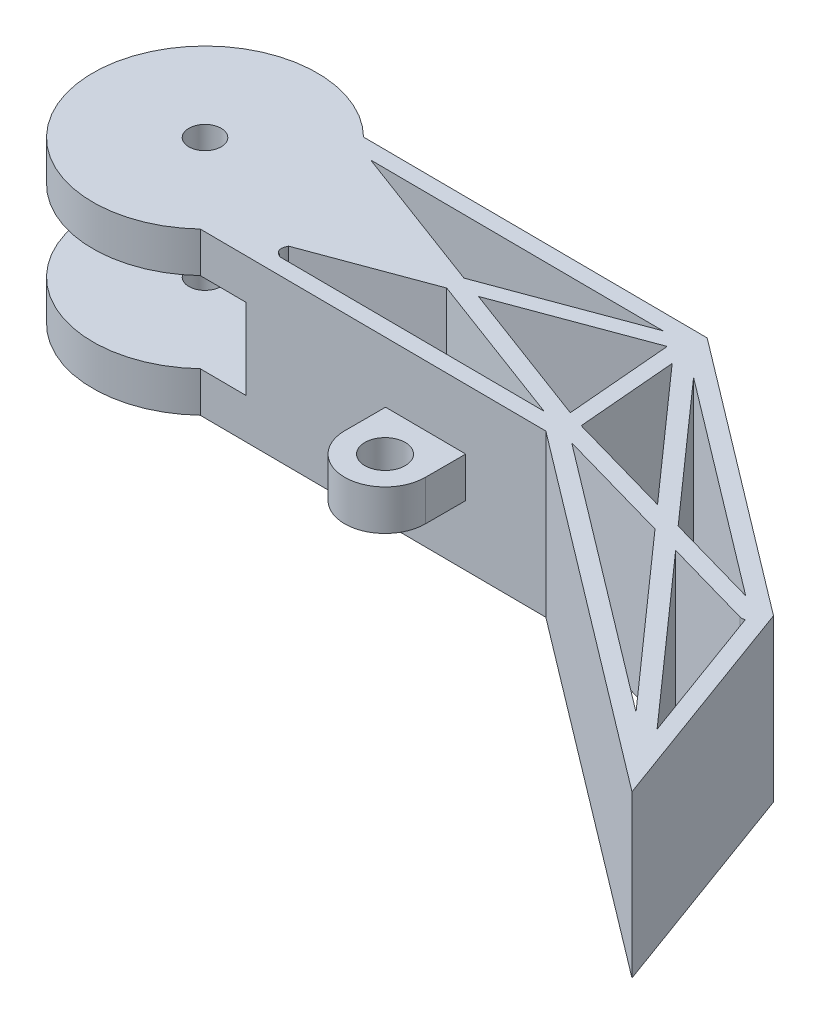
SolidWorks part; units mm, degrees
ref_plane "Front Plane" through (0, 0, 0) normal (0, 0, 1) x (1, 0, 0)
ref_plane "Top Plane" through (0, 0, 0) normal (0, 1, 0) x (1, 0, 0)
ref_plane "Right Plane" through (0, 0, 0) normal (1, 0, 0) x (0, 0, -1)
sketch "Sketch2" plane through (0, 0, 0) normal (0, 1, 0) x (1, 0, 0)
  line L0 (-86.903, -5.6011) -> (-1.9458, -5.6011) construction
  line L1 (-2.39, -19.0095) -> (53.5769, -61.4158)
  line L2 (53.5769, -61.4158) -> (40.7254, -26.2781)
  line L3 (-56.8329, 6.7281) -> (-2.3899, 6.3905)
  line L4 (40.7254, -26.2781) -> (-2.3899, 6.3905)
  line L6 (-57.1469, -18.67) -> (-2.39, -19.0095)
  arc A0 (-57.1469, -18.67) -> (-56.8329, 6.7281) centre (-69.2509, -5.8194) cw
  circle A1 centre (-69.2509, -5.8194) radius 2.54
  dimension "D3" = 25.4
extrude "Boss-Extrude4" add sketch "Sketch2" along normal blind 12.7
sketch "Sketch4" plane through (0, 12.7, 0) normal (0, 1, 0) x (1, 0, 0)
  circle A0 centre (-69.2509, -5.8194) radius 17.6534
extrude "Cut-Extrude1" cut sketch "Sketch4" against normal blind 6.35
sketch "Triangleout" plane through (0, 6.35, 0) normal (0, 1, 0) x (1, 0, 0)
  line L0 (-58.1063, -19.5103) -> (-49.4554, -19.5103)
  line L1 (-49.4554, -19.5103) -> (-53.0939, -12.9324)
  line L2 (-53.0939, -12.9324) -> (-58.1063, -19.5103)
  arc A0 (-57.1469, -18.67) -> (-56.8329, 6.7281) centre (-69.2509, -5.8194) ccw construction
  arc A1 (-56.8329, 6.7281) -> (-57.1469, -18.67) centre (-69.2509, -5.8194) ccw construction
extrude "Cut-Extrude2" cut sketch "Triangleout" along normal blind 6.35
mirror "Mirror3" about plane through (-69.2509, 12.7, 5.8194) normal (0, -1, 0) of "Cut-Extrude2", "Cut-Extrude1", "Boss-Extrude4"
sketch "Sketch5" plane through (0, 25.4, 0) normal (0, 1, 0) x (1, 0, 0)
  line L0 (-1.5294, -16.4748) -> (-3.2505, 3.8558) construction
  line L1 (48.2231, -54.1724) -> (-3.2505, 3.8558)
  line L2 (47.1512, -43.847) -> (-2.39, -6.3095) construction
  line L3 (-57.1312, -16.1301) -> (-3.2505, 3.8558)
  line L4 (53.5769, -61.4158) -> (40.7254, -26.2781) construction
  line L5 (-56.9899, -5.971) -> (-2.39, -6.3095) construction
  line L6 (-57.1469, -18.67) -> (-56.8329, 6.7281) construction
  line L7 (-56.8486, 4.1881) -> (-1.5294, -16.4748)
  line L8 (-1.5294, -16.4748) -> (38.5964, -27.8518)
  line L10 (-56.6895, -17.3208) -> (-3.6238, 2.3628)
  line L11 (47.273, -55.0152) -> (-3.6238, 2.3628)
  line L12 (-57.293, 2.9984) -> (-1.9254, -17.6825)
  line L13 (-1.9254, -17.6825) -> (38.25, -29.0736)
  line L14 (-57.5729, -14.9393) -> (-2.8772, 5.3488)
  line L15 (49.1732, -53.3296) -> (-2.8772, 5.3488)
  line L16 (-56.4043, 5.3778) -> (-1.1333, -15.267)
  line L17 (-1.1333, -15.267) -> (38.9428, -26.6299)
  line L18 (-1.5294, -16.4748) -> (-3.2505, 3.8558)
  line L19 (-0.2639, -16.3676) -> (-1.9851, 3.963)
  line L20 (-2.7949, -16.5819) -> (-4.516, 3.7487)
  line L28 (-3.2505, 3.8558) -> (-56.8486, 4.1881)
  line L29 (38.5964, -27.8518) -> (-3.2505, 3.8558)
  line L30 (48.2231, -54.1724) -> (38.5964, -27.8518)
  line L31 (-1.5294, -16.4748) -> (48.2231, -54.1724)
  line L32 (-57.1312, -16.1301) -> (-1.5294, -16.4748)
  line L33 (-3.2505, 3.8558) -> (-56.8486, 4.1881)
  line L34 (38.5964, -27.8518) -> (-3.2505, 3.8558)
  line L35 (48.2231, -54.1724) -> (38.5964, -27.8518)
  line L36 (-1.5294, -16.4748) -> (48.2231, -54.1724)
  line L37 (-57.1312, -16.1301) -> (-1.5294, -16.4748)
  arc A0 (-56.6895, -17.3208) -> (-57.5729, -14.9393) centre (-57.1312, -16.1301) cw
  arc A1 (47.273, -55.0152) -> (49.1732, -53.3296) centre (48.2231, -54.1724) ccw
  arc A2 (-57.293, 2.9984) -> (-56.4043, 5.3778) centre (-56.8486, 4.1881) cw
  arc A3 (38.25, -29.0736) -> (38.9428, -26.6299) centre (38.5964, -27.8518) ccw
  arc A4 (-0.2639, -16.3676) -> (-2.7949, -16.5819) centre (-1.5294, -16.4748) cw
  arc A5 (-1.9851, 3.963) -> (-4.516, 3.7487) centre (-3.2505, 3.8558) ccw
  arc A7 (-57.1469, -18.67) -> (-56.8329, 6.7281) centre (-69.6889, -5.814) ccw
  spline S0 degree 1 poles (-57.1312, -16.1301) (-56.8486, 4.1881) knots 0 0 1 1
  spline S1 degree 2 poles (-47.0825, -16.1924) (-48.6344, -15.5095) (-47.8598, -14.0456) knots 0 0 0 1 1 1
  dimension "D1" = 2.54
  dimension "D2" = 1.27
  dimension "D3" = 1.27
  dimension "D4" = 1.27
  dimension "D5" = 1.27
extrude "Cut-Extrude5" cut sketch "Sketch5" against normal through all contours L10 L37 L12 | L14 L33 L16 | L16 L20 L10 | A3 L13 L15 L35 | L13 L36 L11 | L17 L34 L15 | L19 L17 L11 region at (36.756, 25.4, 35.0972) region at (21.2871, 25.4, 30.8694) region at (4.8107, 25.4, 11.8628) region at (19.5694, 25.4, 15.7811) region at (-28.9114, 25.4, 13.242) region at (-11.1317, 25.4, 6.1523) region at (-29.8984, 25.4, -1.1482)
sketch3d "3DSketch1"
  point P0 (-32.4826, 11.0258, -6.5771)
sketch3d "3DSketch2"
  point P0 (-24.5315, 25.4, -6.5278)
sketch3d "3DSketch3"
  point P0 (-56.1684, 15.0984, -6.7239)
ref_plane "Plane3" through (-11.7184, 0, 0) normal (-1, 0, 0) x (0, 0, 1)
sketch "Sketch9" plane through (-11.7184, 0, 0) normal (-1, 0, 0) x (0, 0, 1)
  line L0 (-9.2681, 15.875) -> (-7.4382, 16.1357) construction
  line L2 (-6.7281, 19.05) -> (-6.7281, 6.35) construction
  line L3 (-6.7281, 18.415) -> (-6.7281, 6.985)
  line L4 (-9.2681, 9.525) -> (-7.2874, 9.2397) construction
  line L5 (-7.2874, 9.2397) -> (-6.7281, 6.985) construction
  line L6 (-7.4382, 16.1357) -> (-6.7281, 18.415) construction
  arc A0 (-9.2681, 15.875) -> (-9.2681, 9.525) centre (-9.2681, 12.7) ccw
  circle A1 centre (-9.2681, 12.7) radius 1.5875
  spline S0 degree 2 poles (-9.2681, 9.525) (-7.2874, 9.2397) (-6.7281, 6.985) knots 0 0 0 1 1 1
  spline S1 degree 2 poles (-9.2681, 15.875) (-7.4382, 16.1357) (-6.7281, 18.415) knots 0 0 0 1 1 1
  point P0 (-6.7281, 12.7)
  dimension "D2" = 3.175
  dimension "D3" = 3.175
  dimension "D4" = 2.54
  dimension "D5" = 2.54
extrude "Boss-Extrude6" add sketch "Sketch9" along normal blind 3.175 and the other way blind 3.175 separate body
sketch3d "3DSketch4"
  point P0 (0, 0, 0)
ref_plane "Plane4" through (0, 12.7, 0) normal (0, -1, 0) x (1, 0, 0)
sketch "Sketch10" plane through (0, 12.7, 0) normal (0, -1, 0) x (1, 0, 0)
  line L0 (-27.79, 18.852) -> (-15.09, 18.9307)
  line L1 (-57.1469, 18.67) -> (-2.39, 19.0095) construction
  line L2 (-15.09, 18.9307) -> (-15.09, 25.2807)
  line L3 (-27.79, 25.2807) -> (-27.79, 18.852)
  arc A0 (-27.79, 25.2807) -> (-15.09, 25.2807) centre (-21.44, 25.2807) cw
  circle A1 centre (-21.44, 25.2807) radius 3.175
  dimension "D1" = 6.35
  dimension "D2" = 6.35
  dimension "D3" = 6.35
  dimension "D4" = 19.05
extrude "Boss-Extrude7" add sketch "Sketch10" along normal blind 3.175 and the other way blind 3.175
